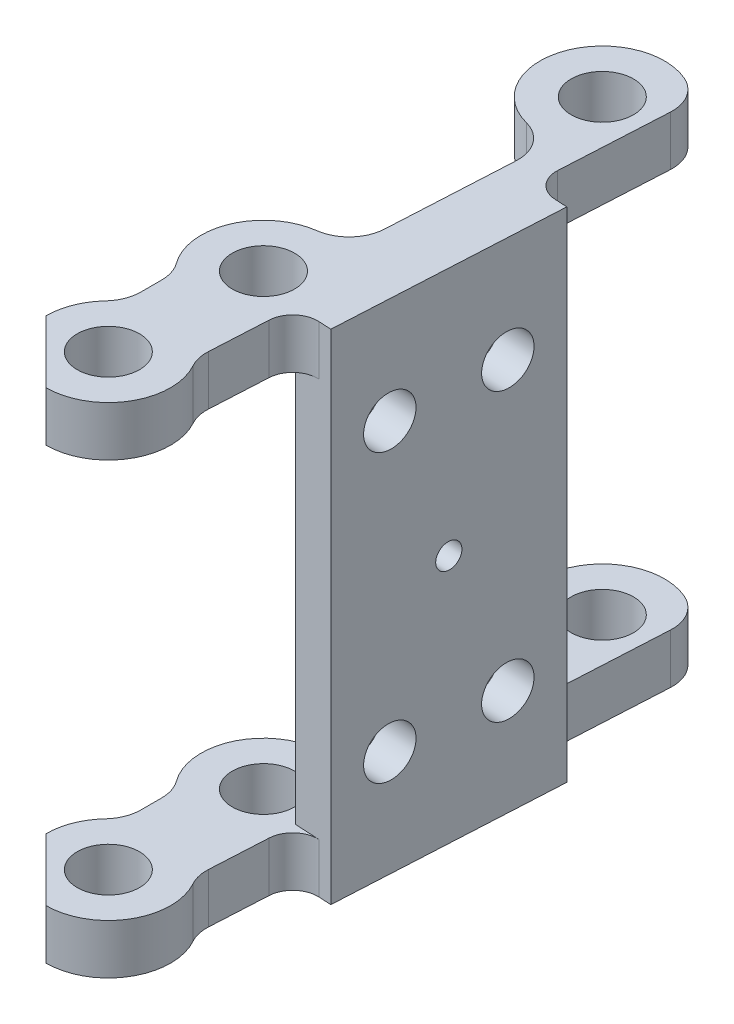
SolidWorks part; units mm, degrees
ref_plane "Front Plane" through (0, 0, 0) normal (0, 0, 1) x (1, 0, 0)
ref_plane "Top Plane" through (0, 0, 0) normal (0, 1, 0) x (1, 0, 0)
ref_plane "Right Plane" through (0, 0, 0) normal (1, 0, 0) x (0, 0, -1)
sketch "Sketch1" plane through (0, 0, 0) normal (0, 1, 0) x (1, 0, 0)
  line L0 (143.3333, 493) -> (716.6667, 493) construction
sketch "Sketch2" plane through (0, 0, 0) normal (0, 1, 0) x (1, 0, 0)
  line L0 (81.4722, 69.2986) -> (86.4722, 64.2986)
  line L1 (83.6263, 73.4096) -> (83.6263, 77.5229)
  line L2 (89.7299, 102.0349) -> (88.8636, 85.8025)
  line L7 (92.4509, 110.0003) -> (90.4247, 72.3609)
  line L8 (92.0481, 102.5189) -> (94.5466, 102.5189)
  line L9 (68.622, 64.6679) -> (68.8091, 64.6679)
  line L10 (82.0956, 50.9646) -> (82.0324, 51.0811)
  line L12 (94.5466, 102.5189) -> (93.4489, 82.1265)
  line L13 (94.0355, 93.0228) -> (93.4252, 81.6866)
  line L14 (93.4252, 81.6866) -> (90.9267, 81.6866)
  line L15 (47.4708, 107.3244) -> (47.5459, 107.4406)
  line L16 (50.5974, 103.1038) -> (50.7762, 103.3805)
  circle A0 centre (86.4722, 69.2986) radius 2.5
  arc A9 (88.8636, 85.8025) -> (83.6263, 77.5229) centre (87.0921, 81.1269) ccw
  arc A10 (83.6263, 73.4096) -> (81.4722, 69.2986) centre (86.4722, 69.2986) ccw
  arc A13 (92.4509, 110.0003) -> (89.7266, 101.9713) centre (88.5782, 106.8376) ccw
  arc A14 (86.4722, 64.2986) -> (90.4247, 72.3609) centre (86.4722, 69.2986) ccw
  circle A15 centre (87.0921, 81.1269) radius 2.5
  circle A18 centre (88.5782, 106.8376) radius 2.5
extrude "Boss-Extrude3" add sketch "Sketch2" along normal blind 4 contours L2 L7 A18 A15 A0 region at (82.4755, 0, -71.3928)
sketch "Sketch3" plane through (0, 4, 0) normal (0, 1, 0) x (1, 0, 0)
  line L0 (91.801, 97.9276) -> (90.8334, 79.9536)
  line L1 (91.801, 97.9276) -> (94.801, 97.7661)
  line L2 (90.8334, 79.9536) -> (93.8334, 79.7922)
  line L3 (94.801, 97.7661) -> (93.8334, 79.7922)
  line L4 (92.4509, 110.0003) -> (90.4247, 72.3609) construction
  dimension "D1" = 3
  dimension "D2" = 18
extrude "Boss-Extrude4" add sketch "Sketch3" against normal blind 40
ref_plane "Plane1" through (0, -16, 0) normal (0, 1, 0) x (1, 0, 0)
mirror "Mirror1" about plane through (0, -16, 0) normal (0, 1, 0) of "Boss-Extrude3"
fillet "Fillet1" radius 2 4 edges at (90.8334, -34, -79.9536) (90.8334, 2, -79.9536) (91.801, -34, -97.9276) (91.801, 2, -97.9276)
sketch "Sketch4" plane through (86.2794, 0, 4.6445) normal (-0.9986, 0, -0.0538) x (-0.0538, 0, 0.9986)
  line L0 (-84.7207, 0) -> (-89.2207, 0) construction
  line L1 (-102.7207, 0) -> (-84.7207, 0) construction
  line L2 (-89.2207, 0) -> (-89.2207, -4.5) construction
  line L3 (-93.7207, 0) -> (-93.7207, -7.4232) construction
  line L4 (-102.7207, -16) -> (-84.7207, -16) construction
  line L6 (-102.7207, -32) -> (-102.7207, 0) construction
  line L7 (-84.7207, -32) -> (-84.7207, 0) construction
  circle A0 centre (-89.2207, -4.5) radius 2
  circle A1 centre (-98.2207, -4.5) radius 2
  circle A2 centre (-89.2207, -27.5) radius 2
  circle A3 centre (-98.2207, -27.5) radius 2
  circle A4 centre (-93.7207, -16) radius 1
extrude "Cut-Extrude1" cut sketch "Sketch4" against normal blind 10
fillet "Fillet3" radius 3 10 edges at (92.4509, -34, -110.0003) (92.4509, 2, -110.0003) (90.4247, -34, -72.3609) (90.4247, 2, -72.3609) (89.7266, -34, -101.9713) (89.7266, 2, -101.9713) (83.6263, 2, -73.4096) (83.6263, 2, -77.5229) (83.6263, -34, -73.4096) (83.6263, -34, -77.5229)
fillet "Fillet4" radius 3 2 edges at (88.8636, -34, -85.8025) (88.8636, 2, -85.8025)
